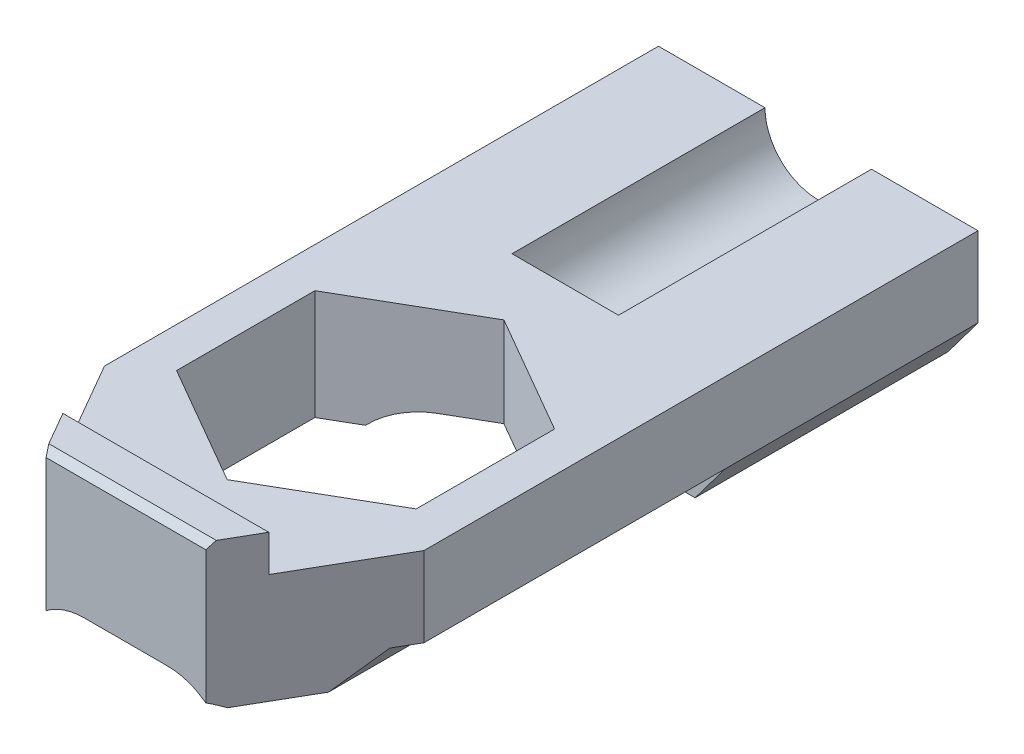
SolidWorks part; units mm, degrees
ref_plane "Ön Düzlem" through (0, 0, 0) normal (0, 0, 1) x (1, 0, 0)
ref_plane "Üst Düzlem" through (0, 0, 0) normal (0, 1, 0) x (1, 0, 0)
ref_plane "Sağ Düzlem" through (0, 0, 0) normal (1, 0, 0) x (0, 0, -1)
sketch "Çizim1" plane through (0, 0, 0) normal (0, 0, 1) x (1, 0, 0)
  line L0 (-8, 0) -> (-24, 0)
  line L1 (-24, 0) -> (-24, -12)
  line L2 (0, -1000) -> (0, 49000) construction
  line L3 (24, 0) -> (24, -12)
  line L4 (8, 0) -> (24, 0)
  line L5 (0, 0) -> (0, -24.5) construction
  line L7 (-16, 0) -> (-16, -44.0357) construction
  line L8 (-19.5, -18) -> (-12.5, -18) construction
  line L9 (-24, -12) -> (-19.5, -18)
  line L10 (-12.5, -18) -> (-10.25, -15)
  line L11 (-10.25, -15) -> (10.25, -15)
  line L12 (-21.75, -15) -> (1.25, -15) construction
  line L13 (12.5, -18) -> (10.25, -15)
  line L14 (19.5, -18) -> (12.5, -18) construction
  line L15 (24, -12) -> (19.5, -18)
  line L16 (-19.5, -18) -> (-12.5, -18)
  line L17 (12.5, -18) -> (19.5, -18)
  arc A0 (-8, 0) -> (8, 0) centre (0, 0) ccw
  point P13 (-16, -18)
  point P21 (0, -15)
  dimension "D1" = 16
  dimension "D2" = 16
  dimension "D3" = 12
  dimension "D4" = 7
  dimension "D5" = 18
  dimension "D6" = 2.25
extrude "Yükseklik-Ekstrüzyon1" add sketch "Çizim1" along normal blind 38 contours L16 L10 L11 L13 L17 L15 L3 L4 A0 L0 L1 L9
fillet "Radyus3" radius 8 2 edges at (10.25, -15, 19) (-10.25, -15, 19)
sketch "Çizim2" plane through (0, 0, 38) normal (0, 0, 1) x (1, 0, 0)
  line L0 (22.125, -12) -> (24, -12)
  line L1 (-24, 0) -> (24, 0)
  line L2 (-24, 0) -> (-24, -12)
  line L3 (-24, -12) -> (-22.125, -12)
  line L4 (24, 0) -> (24, -12)
  line L10 (-6.255, -13.5) -> (6.255, -13.5)
  line L29 (18.75, -16.5) -> (22.8, -11.1)
  line L30 (13.1832, -16.5) -> (18.75, -16.5)
  line L31 (-6.255, -13.5) -> (6.255, -13.5)
  line L32 (-18.75, -16.5) -> (-13.1832, -16.5)
  line L33 (-22.8, -11.1) -> (-18.75, -16.5)
  line L34 (18.75, -16.5) -> (22.125, -12)
  line L35 (13.1832, -16.5) -> (18.75, -16.5)
  line L37 (-18.75, -16.5) -> (-13.1832, -16.5)
  line L38 (-22.125, -12) -> (-18.75, -16.5)
  arc A10 (13.1832, -16.5) -> (6.255, -13.5) centre (6.255, -23) ccw
  arc A11 (-6.255, -13.5) -> (-13.1832, -16.5) centre (-6.255, -23) ccw
  arc A22 (13.1832, -16.5) -> (6.255, -13.5) centre (6.255, -23) ccw
  arc A23 (-6.255, -13.5) -> (-13.1832, -16.5) centre (-6.255, -23) ccw
  point P10 (0, 0)
  dimension "D1" = 1.5
extrude "Yükseklik-Ekstrüzyon2" add sketch "Çizim2" along normal blind 10 contours L34 L0 L4 L1 L2 L3 L38 L37 A23 L10 A22 L35
sketch "Çizim4" plane through (0, 0, 0) normal (1, 0, 0) x (0, 0, -1)
  line L7 (-109, -10.5) -> (-103, -16.5)
  line L8 (-103, -16.5) -> (-48, -16.5)
  line L9 (-48, 0) -> (-48, -16.5)
  line L10 (-48, 0) -> (-98, 0)
  line L12 (-109, -10.5) -> (-109, -0.5)
  line L13 (-109, -0.5) -> (-103, 5.5)
  line L14 (-103, 5.5) -> (-98, 5.5)
  line L15 (-98, 5.5) -> (-98, 0)
  dimension "D1" = 6
  dimension "D2" = 6
  dimension "D3" = 10
  dimension "D4" = 50
  dimension "D5" = 5
  dimension "D8" = 6
  dimension "D9" = 6
extrude "Yükseklik-Ekstrüzyon3" add sketch "Çizim4" against normal mid plane 48 contours L9 L8 L7 L12 L13 L14 L15 L10
sketch "Çizim5" plane through (0, 0, 48) normal (0, 0, -1) x (-1, 0, 0)
  line L2 (24, -16.5) -> (24, -12)
  line L3 (24, -16.5) -> (24, -12)
  line L8 (24, -12) -> (22.125, -12)
  line L9 (24, -12) -> (22.125, -12)
  line L10 (22.125, -12) -> (18.75, -16.5)
  line L11 (22.125, -12) -> (18.75, -16.5)
  line L12 (18.75, -16.5) -> (24, -16.5)
  line L13 (18.75, -16.5) -> (24, -16.5)
  dimension "D1" = 0
extrude "Kes-Ekstrüzyon1" cut sketch "Çizim5" against normal blind 68
sketch "Çizim6" plane through (0, 0, 0) normal (0, 1, 0) x (1, 0, 0)
  line L2 (-24, -83.22) -> (-34.1327, -83.22)
  line L3 (-24, -83.22) -> (-12, -104.0046)
  line L4 (-12, -104.0046) -> (12, -104.0046)
  line L5 (12, -104.0046) -> (24, -83.22)
  line L9 (-34.1327, -83.22) -> (-34.1327, -122.2005)
  line L10 (-34.1327, -122.2005) -> (32.8169, -122.2005)
  line L11 (32.8169, -122.2005) -> (32.8169, -83.22)
  line L12 (32.8169, -83.22) -> (24, -83.22)
  line L14 (12, -62.4354) -> (-12, -62.4354) [skipped]
  line L15 (24, -83.22) -> (18, -72.8277) [skipped]
  line L16 (-18, -72.8277) -> (-24, -83.22) [skipped]
  arc A0 (-18, -93.6123) -> (18, -93.6123) centre (0, -83.22) ccw construction
extrude "Kes-Ekstrüzyon3" cut sketch "Çizim6" against normal blind 68 and the other way blind 68
sketch "Çizim7" plane through (0, 0, 48) normal (0, 0, -1) x (-1, 0, 0)
  line L2 (6.255, -13.5) -> (-6.255, -13.5)
  line L3 (6.255, -13.5) -> (-6.255, -13.5)
  line L4 (-24, -16.5) -> (-18.75, -16.5)
  line L5 (-18.75, -16.5) -> (-22.125, -12)
  line L6 (-22.125, -12) -> (-24, -12)
  line L7 (-24, -12) -> (-24, -16.5)
  line L8 (-24, -16.5) -> (-18.75, -16.5)
  line L9 (-18.75, -16.5) -> (-22.125, -12)
  line L10 (-22.125, -12) -> (-24, -12)
  line L11 (-24, -12) -> (-24, -16.5)
  line L12 (-13.1832, -16.5) -> (13.1832, -16.5)
  line L13 (-13.1832, -16.5) -> (13.1832, -16.5)
  arc A2 (13.1832, -16.5) -> (6.255, -13.5) centre (6.255, -23) ccw
  arc A3 (13.1832, -16.5) -> (6.255, -13.5) centre (6.255, -23) ccw
  arc A4 (-6.255, -13.5) -> (-13.1832, -16.5) centre (-6.255, -23) ccw
  arc A5 (-6.255, -13.5) -> (-13.1832, -16.5) centre (-6.255, -23) ccw
  dimension "D1" = 0
  dimension "D2" = 0
extrude "Kes-Ekstrüzyon4" cut sketch "Çizim7" against normal blind 68
sketch "Çizim9" plane through (0, 0, 0) normal (0, 1, 0) x (1, 0, 0)
  line L0 (-8, -38) -> (-24, -38) construction
  line L1 (-24, -38) -> (-24, -93) construction
  line L3 (0, -38) -> (0, -98) construction
  line L5 (8, -38) -> (-8, -38) construction
  line L19 (-15.4668, -98) -> (15.4668, -98) construction
  line L21 (0, -47.2154) -> (-18, -57.6077)
  line L22 (-18, -57.6077) -> (-18, -78.3923)
  line L23 (-18, -78.3923) -> (0, -88.7846)
  line L24 (0, -88.7846) -> (18, -78.3923)
  line L25 (18, -78.3923) -> (18, -57.6077)
  line L26 (18, -57.6077) -> (0, -47.2154)
  circle A0 centre (0, -68) radius 18 construction
  dimension "D1" = 12
extrude "Kes-Ekstrüzyon7" cut sketch "Çizim9" against normal blind 68
